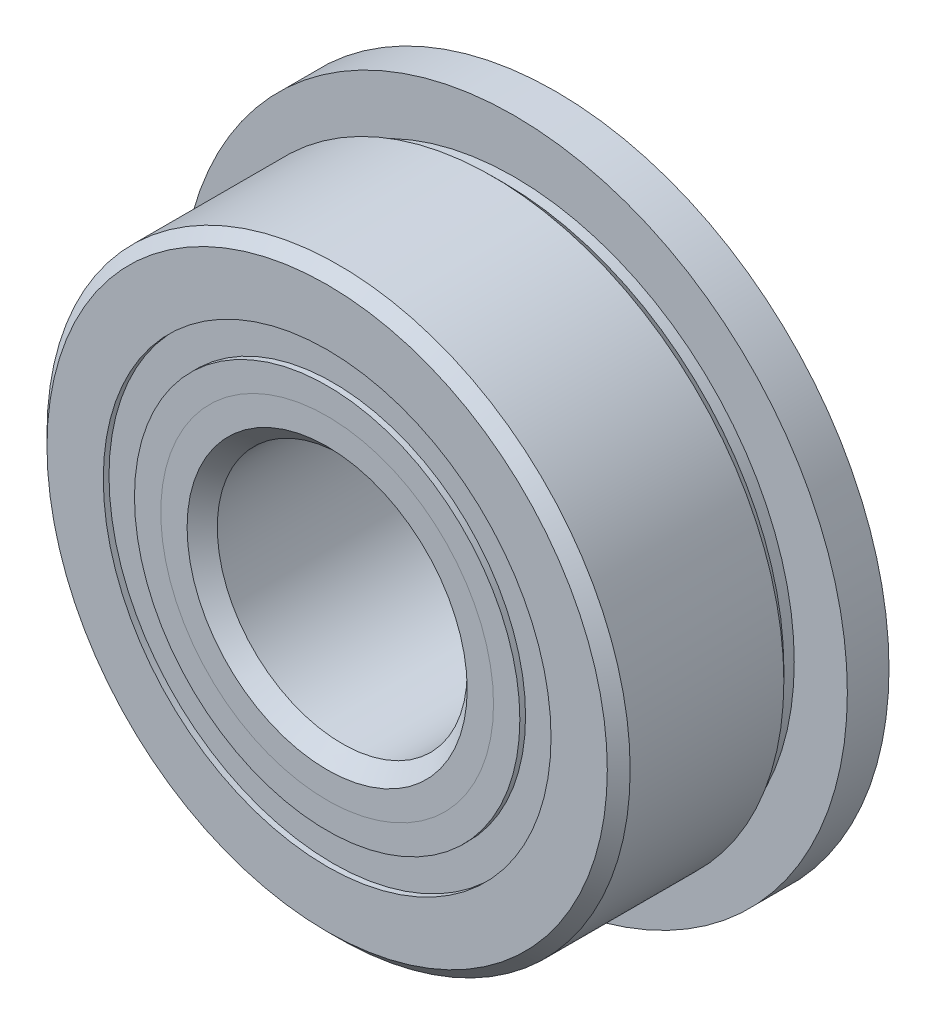
SolidWorks part; units mm, degrees
ref_plane "Front Plane" through (0, 0, 0) normal (0, 0, 1) x (1, 0, 0)
ref_plane "Top Plane" through (0, 0, 0) normal (0, 1, 0) x (1, 0, 0)
ref_plane "Right Plane" through (0, 0, 0) normal (1, 0, 0) x (0, 0, -1)
sketch "Sketch1" plane through (0, 0, 0) normal (1, 0, 0) x (0, 0, -1)
  line L0 (-4.3561, 0) -> (4.3561, 0) construction
  line L1 (0, 11.1125) -> (0, -11.1125) construction
  line L2 (3.9205, 11.1125) -> (-3.9205, 11.1125)
  line L3 (-3.9205, 11.1125) -> (-4.3561, 10.6769)
  line L4 (-4.3561, 10.6769) -> (-4.3561, 8.5315)
  line L5 (-4.3561, 8.5315) -> (-1.936, 8.5315)
  line L6 (4.3561, 8.5315) -> (1.936, 8.5315)
  line L7 (4.3561, 10.6769) -> (4.3561, 8.5315)
  line L8 (3.9205, 11.1125) -> (4.3561, 10.6769)
  line L9 (0, 11.1125) -> (0, 7.9375) construction
  line L10 (0, 7.9375) -> (0, 4.7625) construction
  line L11 (4.3561, 0) -> (5.9627, 0) construction
  arc A0 (-1.936, 8.5315) -> (1.936, 8.5315) centre (0, 7.9375) cw
  point P14 (0, 4.7625)
  dimension "D3" = 3.8721
  dimension "D1" = 45
  dimension "Width" = 8.7122
  dimension "OD" = 22.225
  dimension "D2" = 0.4356
  dimension "Shaft Dia" = 9.525
  dimension "D4" = 0.594
  dimension "Total Wd" = 10.3187
revolve "Revolve1" add sketch "Sketch1" angle 360 about L0
sketch "Sketch2" plane through (0, 0, 0) normal (1, 0, 0) x (0, 0, -1)
  line L0 (-4.3561, 7.3435) -> (-1.936, 7.3435)
  line L1 (-4.3561, 10.6769) -> (-4.3561, -10.6769) construction
  line L2 (-4.3561, 7.3435) -> (-4.3561, 6.3405)
  line L3 (-4.3561, 6.3405) -> (-3.3531, 5.3374)
  line L4 (-3.3531, 5.3374) -> (0, 5.3374)
  line L5 (0, 11.1125) -> (0, -11.1125) construction
  line L6 (0, 5.3374) -> (0, 5.9124)
  line L7 (0, 5.9124) -> (0, 4.7625) construction
  line L8 (-4.3561, 7.3435) -> (-4.3561, 5.3374) construction
  line L9 (-4.3561, 5.3374) -> (-3.3531, 5.3374) construction
  arc A0 (-1.936, 7.3435) -> (0, 5.9124) centre (0, 7.9375) ccw
  arc A1 (1.936, 8.5315) -> (-1.936, 8.5315) centre (0, 7.9375) ccw construction
  circle A2 centre (0, 7.9375) radius 2.0251 construction
  dimension "D1" = 45
revolve "Revolve2" add sketch "Sketch2" angle 360 about L0
sketch "Sketch3" plane through (0, 0, 0) normal (1, 0, 0) x (0, 0, -1)
  line L0 (-4.3561, 6.3405) -> (-3.3531, 5.3374)
  line L1 (-3.3531, 5.3374) -> (0, 5.3374)
  line L2 (0, 5.3374) -> (0, 5.9124)
  line L3 (-4.3561, 6.3405) -> (-4.3561, 5.3374)
  line L4 (-4.3561, 7.3435) -> (-4.3561, 5.3374) construction
  line L5 (-4.3561, 5.3374) -> (-3.7812, 4.7625)
  line L6 (-3.7812, 4.7625) -> (5.527, 4.7625)
  line L8 (5.527, 4.7625) -> (5.9627, 5.1981)
  line L10 (5.9627, 5.1981) -> (5.9627, 7.3435)
  line L11 (5.9627, 7.3435) -> (1.936, 7.3435)
  line L13 (3.9205, 11.1125) -> (4.3561, 10.6769) construction
  circle A0 centre (0, 7.9375) radius 2.0251 construction
  arc A1 (1.936, 7.3435) -> (0, 5.9124) centre (0, 7.9375) cw
revolve "Revolve3" add sketch "Sketch3" angle 360 about L0
sketch "Sketch5" plane through (0, 0, 0) normal (1, 0, 0) x (0, 0, -1)
  line L0 (4.3561, 10.6769) -> (4.3561, 8.5315) construction
  line L1 (4.3561, 9.6042) -> (2.7686, 9.6042)
  line L2 (4.3561, 9.6042) -> (4.3561, 12.7)
  line L3 (4.3561, 12.7) -> (2.7686, 12.7)
  line L4 (2.7686, 9.6042) -> (2.7686, 12.7)
  line L5 (5.9627, 0) -> (-4.3561, 0) construction
  dimension "D1" = 1.5875
  dimension "Flange OD" = 25.4
revolve "Revolve5" add sketch "Sketch5" angle 360 about L5
sketch "Sketch6" plane through (0, 0, 0) normal (1, 0, 0) x (0, 0, -1)
  line L0 (1.9361, 11.1125) -> (2.3717, 10.6769)
  line L1 (3.9205, 11.1125) -> (-3.9205, 11.1125) construction
  line L2 (2.3717, 10.6769) -> (2.7686, 10.6769)
  line L3 (2.7686, 10.6769) -> (2.7686, 11.1125)
  line L4 (2.7686, 11.1125) -> (1.9361, 11.1125)
  line L5 (3.9205, 11.1125) -> (4.3561, 10.6769) construction
  line L6 (2.7686, 9.6042) -> (2.7686, 12.7) construction
  dimension "D1" = 0.3969
revolve "Cut-Revolve1" cut sketch "Sketch6" angle 360 about L0
sketch "Sketch4" plane through (0, 0, 0) normal (1, 0, 0) x (0, 0, -1)
  line L0 (-2.0251, 7.9375) -> (2.0251, 7.9375)
  circle A1 centre (0, 7.9375) radius 2.0251 construction
  arc A2 (-2.0251, 7.9375) -> (2.0251, 7.9375) centre (0, 7.9375) cw
  arc A3 (1.936, 8.5315) -> (-1.936, 8.5315) centre (0, 7.9375) ccw construction
revolve "Revolve4" add sketch "Sketch4" angle 360 about L0
ref_axis "Axis1" through (0, 0, -4.3561) along (0, 0, 1)
pattern_circular "CirPattern1" count 12 over 360 about axis through (0, 0, -4.3561) along (0, 0, 1) of bodies 104
sketch "Sketch7" plane through (0, 0, 0) normal (1, 0, 0) x (0, 0, -1)
  line L0 (-4.3561, 8.5315) -> (-1.936, 8.5315) construction
  line L1 (-4.1383, 8.5315) -> (-2.0251, 8.5315)
  line L2 (-4.1383, 8.5315) -> (-4.1383, 7.3435)
  line L3 (-4.1383, 7.3435) -> (-2.0251, 7.3435)
  line L4 (-2.0251, 8.5315) -> (-2.0251, 7.3435)
  line L5 (-4.3561, 7.3435) -> (-1.936, 7.3435) construction
  line L6 (-3.9205, 11.1125) -> (-4.3561, 10.6769) construction
  line L7 (4.3561, 8.5315) -> (1.936, 8.5315) construction
  line L8 (4.1383, 8.5315) -> (2.0251, 8.5315)
  line L9 (4.1383, 8.5315) -> (4.1383, 7.3435)
  line L10 (4.1383, 7.3435) -> (2.0251, 7.3435)
  line L11 (2.0251, 8.5315) -> (2.0251, 7.3435)
  line L12 (5.9627, 7.3435) -> (1.936, 7.3435) construction
  line L13 (3.9205, 11.1125) -> (4.3561, 10.6769) construction
  circle A0 centre (0, 7.9375) radius 2.0251 construction
  point P10 (-4.1383, 10.8947)
  point P21 (4.1383, 10.8947)
revolve "Revolve6" add sketch "Sketch7" angle 360 about L0
equation "\"D2@Sketch1\" = \"Width@Sketch1\"*.05"
equation "\"D3@Sketch1\" = \"Width@Sketch1\"/2.25"
equation "\"D4@Sketch1\" = (((\"OD@Sketch1\"-\"Width@Sketch1\")/2)/3.25)/3.5"
equation "\"D2@CirPattern1\" = 360/\"Balls@CirPattern1\""
